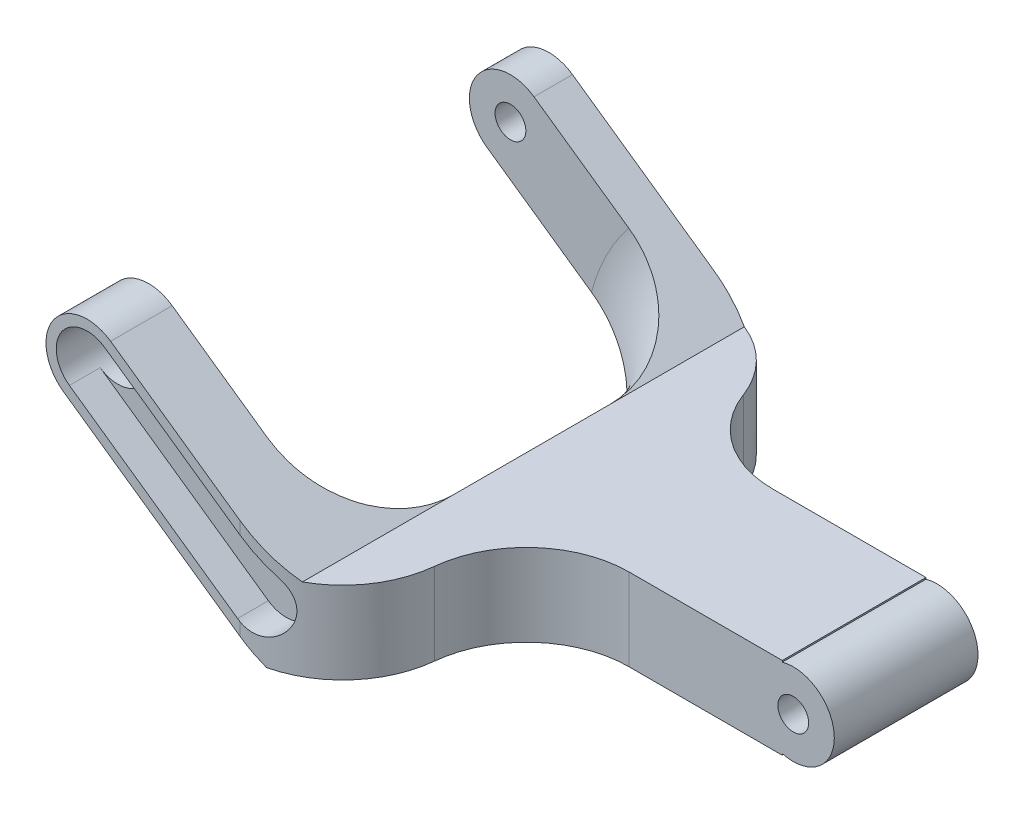
SolidWorks part; units mm, degrees
ref_plane "前视基准面" through (0, 0, 0) normal (0, 0, 1) x (1, 0, 0)
ref_plane "上视基准面" through (0, 0, 0) normal (0, 1, 0) x (1, 0, 0)
ref_plane "右视基准面" through (0, 0, 0) normal (1, 0, 0) x (0, 0, -1)
sketch "草图1" plane through (0, 0, 0) normal (0, 0, 1) x (1, 0, 0)
  line L0 (15.6052, 4.0165) -> (15.6052, 4.1614)
  line L1 (15.6052, -3.8386) -> (-14.3948, -3.8386)
  line L2 (15.6052, -3.8386) -> (15.6052, -3.6938)
  line L3 (15.6052, 4.1614) -> (-16.9172, 4.1614)
  line L7 (-14.3948, -3.8386) -> (-31.8334, -16.0492)
  line L8 (-36.422, -9.496) -> (-16.9172, 4.1614)
  line L9 (-34.1277, -1012.7726) -> (-34.1277, 48987.2274) construction
  line L10 (16.6718, -999.8386) -> (16.6718, 49000.1614) construction
  arc A0 (15.6052, -3.6938) -> (15.6052, 4.0165) centre (16.6718, 0.1614) ccw
  arc A1 (-36.422, -9.496) -> (-31.8334, -16.0492) centre (-34.1277, -12.7726) ccw
  circle A2 centre (-34.1277, -12.7726) radius 1.5
  circle A3 centre (16.6718, 0.1614) radius 1.5
  point P0 (0, 0)
  dimension "D3" = 8
  dimension "D6" = 8
  dimension "D7" = 3
  dimension "D8" = 3
  dimension "D1" = 8
  dimension "D2" = 30
  dimension "D4" = 145
  dimension "D5" = 8
  dimension "D9" = 50.7995
extrude "凸台-拉伸2" add sketch "草图1" along normal blind 50
sketch "草图14" plane through (0, -3.8386, 0) normal (0, -1, 0) x (1, 0, 0)
  line L0 (-16.9172, 25) -> (49983.0828, 25) construction
  line L1 (-16.9172, 50) -> (-16.9172, 0) construction
  line L2 (20.6718, 50) -> (20.6718, 32)
  line L3 (20.6718, 0) -> (-9.3282, 0)
  line L4 (20.6718, 0) -> (20.6718, 18)
  line L5 (20.6718, 18) -> (-9.3282, 18)
  line L6 (-9.3282, 0) -> (-9.3282, 18)
  line L7 (20.6718, 50) -> (-9.3282, 50)
  line L8 (20.6718, 32) -> (-9.3282, 32)
  line L9 (-9.3282, 50) -> (-9.3282, 32)
  point P4 (-16.9172, 25)
  dimension "D1" = 7
  dimension "D2" = 30
extrude "切除-拉伸6" cut sketch "草图14" against normal through all
sketch "草图15" plane through (0, 4.1614, 0) normal (0, 1, 0) x (1, 0, 0)
  line L0 (20.6718, -25) -> (-49979.3282, -25) construction
  line L1 (20.6718, -32) -> (20.6718, -18) construction
  line L2 (-16.9172, -50) -> (-16.9172, 0) construction
  line L3 (-39.3648, -25) -> (-16.9172, -25)
  line L4 (-39.3648, -25) -> (-39.3648, -8.75)
  line L5 (-39.3648, -8.75) -> (-16.9172, -8.75)
  line L6 (-16.9172, -25) -> (-16.9172, -8.75)
  point P4 (20.6718, -25)
  dimension "D1" = 16.25
  dimension "D2" = 22.4476
extrude "切除-拉伸7" cut sketch "草图15" against normal blind 30
sketch "草图17" plane through (0, 4.1614, 0) normal (0, 1, 0) x (1, 0, 0)
  line L1 (-16.9172, -25) -> (-42.2771, -25)
  line L2 (-16.9172, -25) -> (-16.9172, -44)
  line L3 (-16.9172, -44) -> (-42.2771, -44)
  line L4 (-42.2771, -25) -> (-42.2771, -44)
  dimension "D1" = 19
  dimension "D2" = 25.3598
extrude "切除-拉伸9" cut sketch "草图17" against normal blind 30
fillet "圆角8" radius 10 1 edges at (-16.9172, -5.6048, 26.375)
sketch "草图19" plane through (-7.5208, 10.7408, 0) normal (-0.5736, 0.8192, 0) x (0.8192, 0.5736, 0)
  line L1 (-39.2819, 0) -> (-5.2543, 0)
  line L2 (-39.2819, 0) -> (-39.2819, -5)
  line L3 (-39.2819, -5) -> (-5.2543, -5)
  line L4 (-5.2543, 0) -> (-5.2543, -5)
  line L5 (-5.2543, -18) -> (-5.2543, 0) construction
  dimension "D1" = 5
  dimension "D2" = 34.0275
extrude "切除-拉伸11" cut sketch "草图19" against normal through all
fillet "圆角9" radius 10 2 edges at (-9.3282, 0.1614, 32) (-9.3282, 0.1614, 18)
fillet "圆角11" radius 10 4 edges at (-16.9172, 3.4812, 44) (-16.9172, 3.4812, 8.75) (-16.2654, -0.7503, 44) (-16.2654, -0.7503, 8.75)
fillet "圆角12" radius 10 2 edges at (-9.3282, 0.1614, 50) (-9.3282, 0.1614, 5)
sketch "草图20" plane through (0, 0, 50) normal (0, 0, 1) x (1, 0, 0)
  line L0 (-35.8484, -10.3152) -> (-19.4654, 1.1564)
  line L1 (-32.407, -15.2301) -> (-16.0239, -3.7586)
  line L2 (-852.8272, -586.0322) -> (-36.5852, -14.4934) construction
  line L3 (-19.2279, 2.5434) -> (-36.422, -9.496) construction
  line L4 (-15.2872, 0.4196) -> (40923.9271, 28666.3661) construction
  line L5 (-32.4894, -11.6255) -> (-27.1418, -7.8811) construction
  arc A0 (-35.8484, -10.3152) -> (-32.407, -15.2301) centre (-34.1277, -12.7726) ccw
  arc A1 (-16.0239, -3.7586) -> (-19.4654, 1.1564) centre (-17.7447, -1.3011) ccw
  dimension "D1" = 3
  dimension "D2" = 20
extrude "切除-拉伸12" cut sketch "草图20" against normal blind 3
sketch "草图21" plane through (0, 0, 44) normal (0, 0, -1) x (-1, 0, 0)
  circle A0 centre (34.1277, -12.7726) radius 3
  dimension "D1" = 6
extrude "切除-拉伸13" cut sketch "草图21" against normal blind 5
ref_plane "基准面1" through (0, 14.1614, 0) normal (0, 1, 0) x (1, 0, 0)
mirror "镜向1" about plane through (0, 14.1614, 0) normal (0, 1, 0) of bodies 123
delete or keep bodies "实体-删除/保留 1" type delete bodies bodies 123
